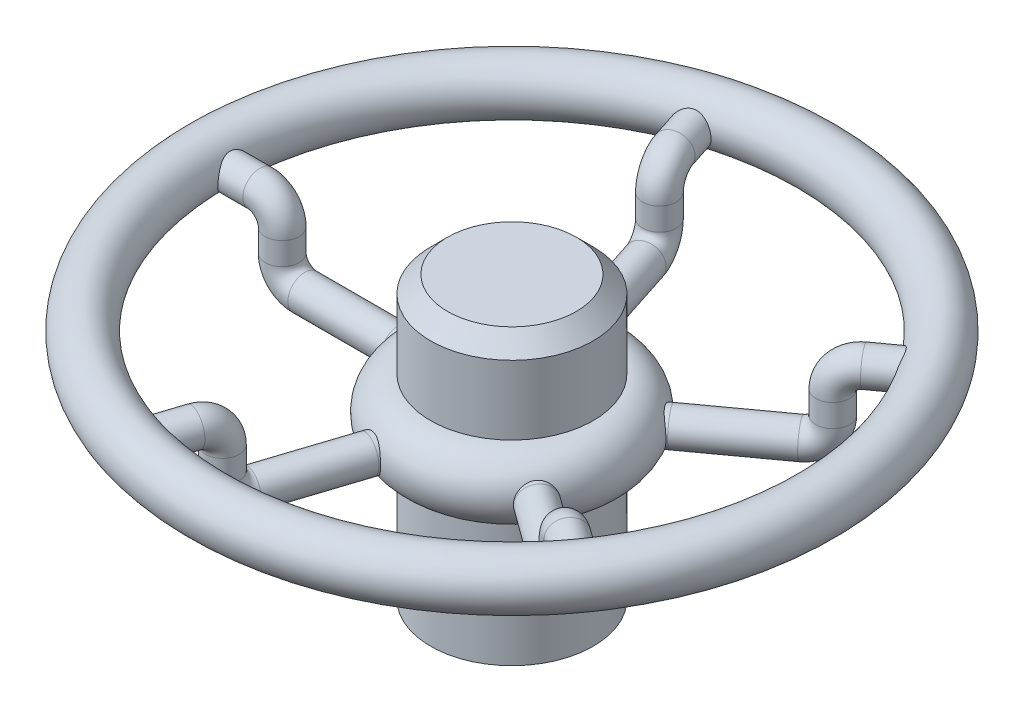
SolidWorks part; units mm, degrees
material "Chrome Stainless Steel"
ref_plane "Front Plane" through (0, 0, 0) normal (0, 0, 1) x (1, 0, 0)
ref_plane "Top Plane" through (0, 0, 0) normal (0, 1, 0) x (1, 0, 0)
ref_plane "Right Plane" through (0, 0, 0) normal (1, 0, 0) x (0, 0, -1)
sketch "Sketch1" plane through (0, 0, 0) normal (0, 0, 1) x (1, 0, 0)
  line L0 (0, 0) -> (0, 35.1124)
  line L1 (0, 35.1124) -> (-28.6101, 35.1124)
  line L2 (-28.6101, 35.1124) -> (-36.1528, 27.5698)
  line L3 (-36.1528, 27.5698) -> (-36.1528, -3.1211)
  line L4 (-36.1528, -32.2514) -> (-36.1528, -62.9423)
  line L5 (-36.1528, -62.9423) -> (0, -62.9423)
  line L6 (0, -62.9423) -> (0, 0)
  arc A0 (-36.1528, -3.1211) -> (-36.1528, -32.2514) centre (-36.1528, -17.6863) ccw
revolve "Revolve1" add sketch "Sketch1" angle 360 about L6
sketch "Sketch2" plane through (0, 0, 0) normal (0, 0, 1) x (1, 0, 0)
  line L0 (-50.718, -17.6863) -> (0, -17.6863)
  line L1 (-50.718, -17.6863) -> (-92.0756, -17.6863)
  line L2 (-102.0756, -7.6863) -> (-102.0756, 2.3416)
  line L3 (-112.0756, 12.3416) -> (-134.8866, 12.3416)
  arc A0 (-36.1528, -3.1211) -> (-36.1528, -32.2514) centre (-36.1528, -17.6863) ccw construction
  arc A1 (-92.0756, -17.6863) -> (-102.0756, -7.6863) centre (-92.0756, -7.6863) cw
  arc A2 (-102.0756, 2.3416) -> (-112.0756, 12.3416) centre (-112.0756, 2.3416) ccw
  dimension "D1" = 10
ref_plane "Plane1" through (-134.8866, 12.3416, 0) normal (-1, 0, 0) x (0, 0, 1)
sketch "Sketch3" plane through (-134.8866, 12.3416, 0) normal (-1, 0, 0) x (0, 0, 1)
sweep "Sweep3" add path "Sketch2" circular profile diameter 15 parameters "D3"=15
sketch "Sketch34" plane through (0, 0, 0) normal (0, 0, 1) x (1, 0, 0)
  line L0 (0, -62.9423) -> (0, 0) construction
  line L1 (-36.1528, -62.9423) -> (36.1528, -62.9423) construction
pattern_circular "CirPattern2" count 5 over 360 about axis through (0, -62.9423, 0) along (0, -1, 0) of "Sweep3" reverse direction yes
sketch "Sketch39" plane through (0, 0, 0) normal (0, 0, 1) x (1, 0, 0)
  line L0 (-134.8866, 24.8876) -> (-134.8866, -0.2045) construction
  circle A0 centre (-134.8866, 13.3216) radius 11.5859
revolve "Revolve3" add sketch "Sketch39" angle 360 about L0
sketch "Sketch40" plane through (0, -62.9423, 0) normal (0, -1, 0) x (1, 0, 0)
  circle A0 centre (0, 0) radius 36.1528
extrude "Boss-Extrude3" add sketch "Sketch40" along normal blind 27
sketch "Sketch42" plane through (0, -89.9423, 0) normal (0, -1, 0) x (1, 0, 0)
  circle A0 centre (0, 0) radius 19.2298
extrude "Cut-Extrude5" cut sketch "Sketch42" against normal blind 27
sketch "Sketch43" plane through (0, -62.9423, 0) normal (0, -1, 0) x (1, 0, 0)
  circle A0 centre (0, 0) radius 9.3535
extrude "Cut-Extrude6" cut sketch "Sketch43" against normal blind 27
